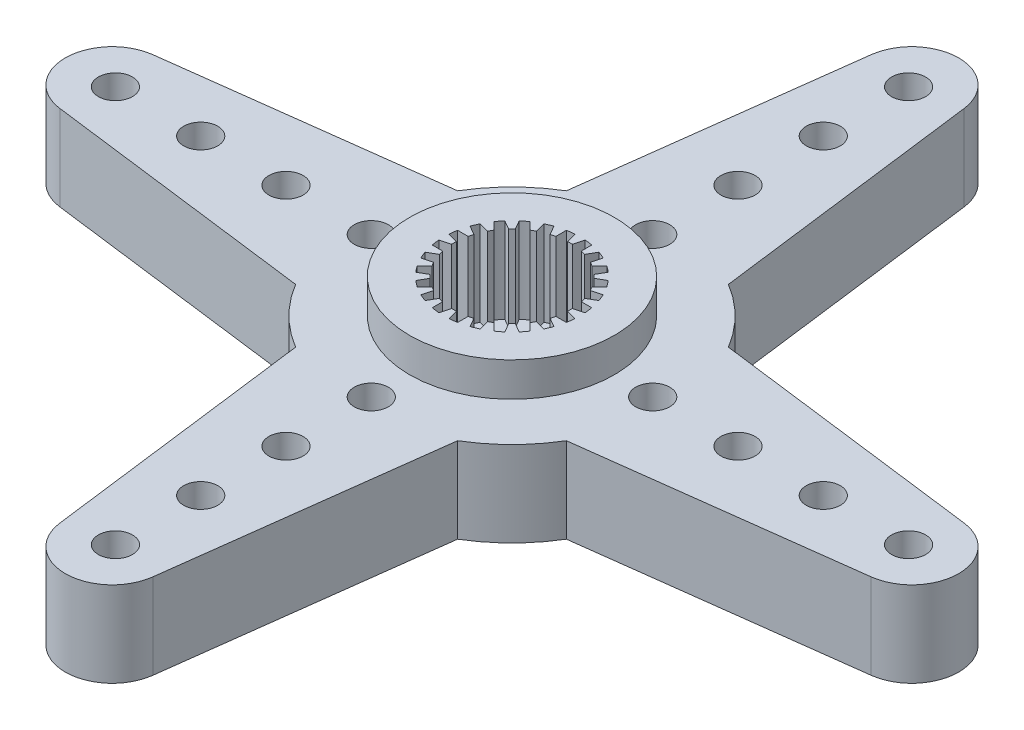
SolidWorks part; units mm, degrees
ref_plane "Plan de face" through (0, 0, 0) normal (0, 0, 1) x (1, 0, 0)
ref_plane "Plan de dessus" through (0, 0, 0) normal (0, 1, 0) x (1, 0, 0)
ref_plane "Plan de droite" through (0, 0, 0) normal (1, 0, 0) x (0, 0, -1)
sketch "Esquisse1" plane through (0, 0, 0) normal (0, 1, 0) x (1, 0, 0)
  circle A0 centre (0, 0) radius 9.25
  circle A1 centre (0, 0) radius 1.65
  dimension "D1" = 18.5
  dimension "D2" = 3.3
extrude "Boss.-Extru.1" add sketch "Esquisse1" along normal blind 8
sketch "Esquisse2" plane through (0, 8, 0) normal (0, 1, 0) x (1, 0, 0)
  line L0 (-4.75, 7.9373) -> (-2.7279, 23.7853)
  line L1 (2.7279, 23.7853) -> (4.75, 7.9373)
  line L2 (4.75, 7.9373) -> (-4.75, 7.9373)
  line L3 (-9.6717, 26.1873) -> (9.6602, 26.1873) construction
  circle A0 centre (0, 0) radius 9.25 construction
  arc A1 (-2.7279, 23.7853) -> (2.7279, 23.7853) centre (0, 23.4373) cw
  dimension "D3" = 2.75
  dimension "D1" = 9.5
  dimension "D2" = 18.25
extrude "Boss.-Extru.2" add sketch "Esquisse2" against normal up to surface (8 mm away) up to face at (0, 0, 9.25)
pattern_circular "Répétition circulaire1" count 4 over 360 about axis through (0, 8, 0) along (0, -1, 0) of "Boss.-Extru.2" reverse direction yes
sketch "Esquisse3" plane through (0, 8, 0) normal (0, 1, 0) x (1, 0, 0)
  line L0 (0, 0) -> (0, 17.0578) construction
  circle A0 centre (0, 8.25) radius 1
  dimension "D1" = 2
  dimension "D2" = 8.25
extrude "Enlèv. mat.-Extru.1" cut sketch "Esquisse3" against normal blind 8
pattern_linear "Répétition linéaire1" count 4 spacing 5 along (0, 0, -1) of "Enlèv. mat.-Extru.1"
pattern_circular "Répétition circulaire2" count 4 over 360 about axis through (0, 8, 0) along (0, -1, 0) of "Enlèv. mat.-Extru.1", "Répétition linéaire1"
sketch "Esquisse4" plane through (0, 8, 0) normal (0, 1, 0) x (1, 0, 0)
  line L1 (-37.0652, 32.1232) -> (36.96, 32.1232)
  line L2 (-37.0652, 32.1232) -> (-37.0652, -32.9644)
  line L3 (-37.0652, -32.9644) -> (36.96, -32.9644)
  line L4 (36.96, 32.1232) -> (36.96, -32.9644)
  circle A0 centre (0, 0) radius 6
  dimension "D2" = 12
extrude "Enlèv. mat.-Extru.2" cut sketch "Esquisse4" against normal blind 2
sketch "Esquisse5" plane through (0, 8, 0) normal (0, 1, 0) x (1, 0, 0)
  circle A0 centre (0, 0) radius 4
  dimension "D1" = 8
extrude "Enlèv. mat.-Extru.3" cut sketch "Esquisse5" against normal blind 5
sketch "Esquisse6" plane through (0, 8, 0) normal (0, 1, 0) x (1, 0, 0)
  line L0 (0, 0) -> (0, 6.8792) construction
  line L1 (0, 6.8792) -> (-2.9166, 4) construction
  line L2 (-2.9166, 4) -> (2.5197, 4) construction
  line L3 (-0.3, 4) -> (-0.1392, 3.4)
  line L4 (-0.1392, 3.4) -> (0.1392, 3.4)
  line L5 (0.1392, 3.4) -> (0.3, 4)
  line L6 (0.3, 4) -> (-0.3, 4)
  circle A0 centre (0, 0) radius 4 construction
  point P9 (-0.2117, 3.4)
  point P12 (-0.2005, 3.4)
  dimension "D1" = 0.6
  dimension "D2" = 0.6
  dimension "D3" = 15
extrude "Boss.-Extru.3" add sketch "Esquisse6" against normal up to surface (5 mm away) up to face at (0, 3, 1.65)
pattern_circular "Répétition circulaire3" count 24 over 360 about axis through (0, 8, 0) along (0, -1, 0) of "Boss.-Extru.3"
sketch "Esquisse7" plane through (0, 0, 0) normal (0, -1, 0) x (1, 0, 0)
  circle A0 centre (0, 0) radius 4.5
  circle A1 centre (0, 0) radius 34.023
  dimension "D1" = 9
extrude "Enlèv. mat.-Extru.4" cut sketch "Esquisse7" against normal blind 1
sketch "Esquisse8" plane through (0, 0, 0) normal (0, -1, 0) x (1, 0, 0)
  circle A0 centre (0, 0) radius 2.75
  dimension "D1" = 5.5
extrude "Enlèv. mat.-Extru.5" cut sketch "Esquisse8" against normal blind 1
chamfer "Chanfrein1" distance 1 angle 45 1 edges at (0, 1, -4.5)
